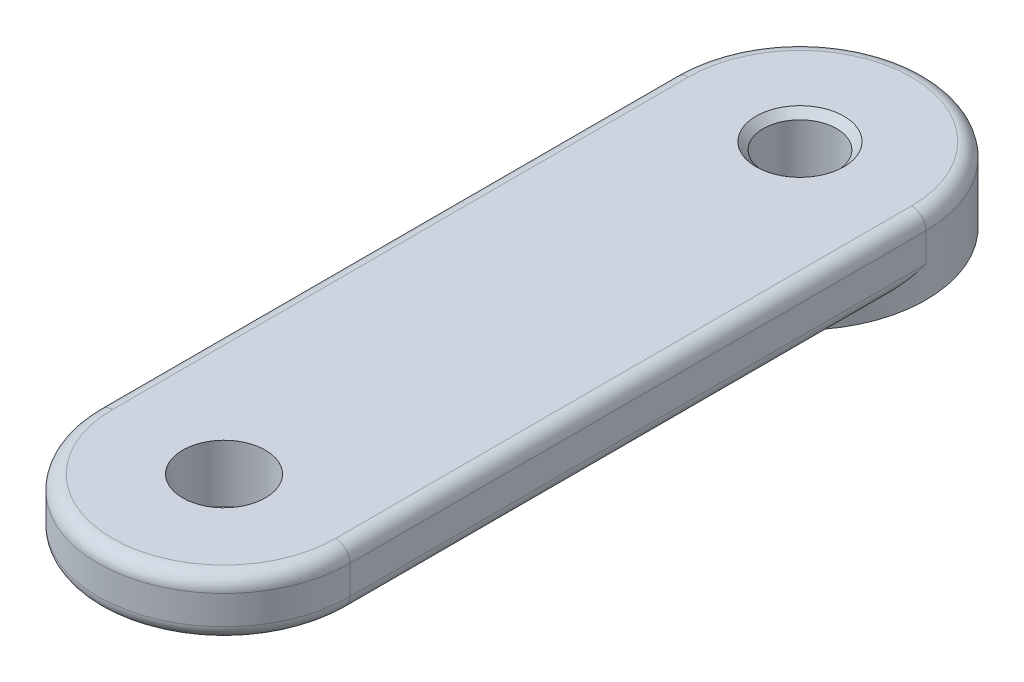
SolidWorks part; units mm, degrees
ref_plane "Front Plane" through (0, 0, 0) normal (0, 0, 1) x (1, 0, 0)
ref_plane "Top Plane" through (0, 0, 0) normal (0, 1, 0) x (1, 0, 0)
ref_plane "Right Plane" through (0, 0, 0) normal (1, 0, 0) x (0, 0, -1)
sketch "Sketch1" plane through (0, 0, 0) normal (0, 1, 0) x (1, 0, 0)
  line L0 (-8.75, 0) -> (-8.75, 40)
  line L1 (-8.75, 40) -> (0, 40) construction
  line L2 (8.75, 40) -> (8.75, 0)
  arc A0 (-8.75, 0) -> (8.75, 0) centre (0, 0) ccw
  arc A1 (8.75, 40) -> (-8.75, 40) centre (0, 40) ccw
  circle A2 centre (0, 40) radius 2.55
  circle A3 centre (0, 0) radius 2.875
  dimension "D1" = 17.5
  dimension "D2" = 5.75
  dimension "D3" = 5.1
  dimension "D4" = 40
extrude "Boss-Extrude1" add sketch "Sketch1" along normal blind 4
sketch "Sketch2" plane through (0, 4, 0) normal (0, 1, 0) x (1, 0, 0)
  arc A0 (-0.5856, -4.3609) -> (-0.1996, -3.4933) centre (-1.7886, -3.306) ccw
  arc A1 (-0.1996, -3.4933) -> (0.1996, -3.4933) centre (0, 0) ccw
  arc A2 (0.1996, -3.4933) -> (0.5856, -4.3609) centre (1.7886, -3.306) ccw
  arc A3 (0.5856, -4.3609) -> (0.7906, -4.3284) centre (0, 0) ccw
  arc A4 (0.7906, -4.3284) -> (0.8897, -3.384) centre (-0.6795, -3.6969) ccw
  arc A5 (0.8897, -3.384) -> (1.2693, -3.2607) centre (0, 0) ccw
  arc A6 (1.2693, -3.2607) -> (1.9045, -3.9665) centre (2.7226, -2.5914) ccw
  arc A7 (1.9045, -3.9665) -> (2.0895, -3.8722) centre (0, 0) ccw
  arc A8 (2.0895, -3.8722) -> (1.8918, -2.9435) centre (0.4962, -3.7259) ccw
  arc A9 (1.8918, -2.9435) -> (2.2148, -2.7088) centre (0, 0) ccw
  arc A10 (2.2148, -2.7088) -> (3.037, -3.1838) centre (3.3902, -1.6233) ccw
  arc A11 (3.037, -3.1838) -> (3.1838, -3.037) centre (0, 0) ccw
  arc A12 (3.1838, -3.037) -> (2.7088, -2.2148) centre (1.6233, -3.3902) ccw
  arc A13 (2.7088, -2.2148) -> (2.9435, -1.8918) centre (0, 0) ccw
  arc A14 (2.9435, -1.8918) -> (3.8722, -2.0895) centre (3.7259, -0.4962) ccw
  arc A15 (3.8722, -2.0895) -> (3.9665, -1.9045) centre (0, 0) ccw
  arc A16 (3.9665, -1.9045) -> (3.2607, -1.2693) centre (2.5914, -2.7226) ccw
  arc A17 (3.2607, -1.2693) -> (3.384, -0.8897) centre (0, 0) ccw
  arc A18 (3.384, -0.8897) -> (4.3284, -0.7906) centre (3.6969, 0.6795) ccw
  arc A19 (4.3284, -0.7906) -> (4.3609, -0.5856) centre (0, 0) ccw
  arc A20 (4.3609, -0.5856) -> (3.4933, -0.1996) centre (3.306, -1.7886) ccw
  arc A21 (3.4933, -0.1996) -> (3.4933, 0.1996) centre (0, 0) ccw
  arc A22 (3.4933, 0.1996) -> (4.3609, 0.5856) centre (3.306, 1.7886) ccw
  arc A23 (4.3609, 0.5856) -> (4.3284, 0.7906) centre (0, 0) ccw
  arc A24 (4.3284, 0.7906) -> (3.384, 0.8897) centre (3.6969, -0.6795) ccw
  arc A25 (3.384, 0.8897) -> (3.2607, 1.2693) centre (0, 0) ccw
  arc A26 (3.2607, 1.2693) -> (3.9665, 1.9045) centre (2.5914, 2.7226) ccw
  arc A27 (3.9665, 1.9045) -> (3.8722, 2.0895) centre (0, 0) ccw
  arc A28 (3.8722, 2.0895) -> (2.9435, 1.8918) centre (3.7259, 0.4962) ccw
  arc A29 (2.9435, 1.8918) -> (2.7088, 2.2148) centre (0, 0) ccw
  arc A30 (2.7088, 2.2148) -> (3.1838, 3.037) centre (1.6233, 3.3902) ccw
  arc A31 (3.1838, 3.037) -> (3.037, 3.1838) centre (0, 0) ccw
  arc A32 (3.037, 3.1838) -> (2.2148, 2.7088) centre (3.3902, 1.6233) ccw
  arc A33 (2.2148, 2.7088) -> (1.8918, 2.9435) centre (0, 0) ccw
  arc A34 (1.8918, 2.9435) -> (2.0895, 3.8722) centre (0.4962, 3.7259) ccw
  arc A35 (2.0895, 3.8722) -> (1.9045, 3.9665) centre (0, 0) ccw
  arc A36 (1.9045, 3.9665) -> (1.2693, 3.2607) centre (2.7226, 2.5914) ccw
  arc A37 (1.2693, 3.2607) -> (0.8897, 3.384) centre (0, 0) ccw
  arc A38 (0.8897, 3.384) -> (0.7906, 4.3284) centre (-0.6795, 3.6969) ccw
  arc A39 (0.7906, 4.3284) -> (0.5856, 4.3609) centre (0, 0) ccw
  arc A40 (0.5856, 4.3609) -> (0.1996, 3.4933) centre (1.7886, 3.306) ccw
  arc A41 (0.1996, 3.4933) -> (-0.1996, 3.4933) centre (0, 0) ccw
  arc A42 (-0.1996, 3.4933) -> (-0.5856, 4.3609) centre (-1.7886, 3.306) ccw
  arc A43 (-0.5856, 4.3609) -> (-0.7906, 4.3284) centre (0, 0) ccw
  arc A44 (-0.7906, 4.3284) -> (-0.8897, 3.384) centre (0.6795, 3.6969) ccw
  arc A45 (-0.8897, 3.384) -> (-1.2693, 3.2607) centre (0, 0) ccw
  arc A46 (-1.2693, 3.2607) -> (-1.9045, 3.9665) centre (-2.7226, 2.5914) ccw
  arc A47 (-1.9045, 3.9665) -> (-2.0895, 3.8722) centre (0, 0) ccw
  arc A48 (-2.0895, 3.8722) -> (-1.8918, 2.9435) centre (-0.4962, 3.7259) ccw
  arc A49 (-1.8918, 2.9435) -> (-2.2148, 2.7088) centre (0, 0) ccw
  arc A50 (-2.2148, 2.7088) -> (-3.037, 3.1838) centre (-3.3902, 1.6233) ccw
  arc A51 (-3.037, 3.1838) -> (-3.1838, 3.037) centre (0, 0) ccw
  arc A52 (-3.1838, 3.037) -> (-2.7088, 2.2148) centre (-1.6233, 3.3902) ccw
  arc A53 (-2.7088, 2.2148) -> (-2.9435, 1.8918) centre (0, 0) ccw
  arc A54 (-2.9435, 1.8918) -> (-3.8722, 2.0895) centre (-3.7259, 0.4962) ccw
  arc A55 (-3.8722, 2.0895) -> (-3.9665, 1.9045) centre (0, 0) ccw
  arc A56 (-3.9665, 1.9045) -> (-3.2607, 1.2693) centre (-2.5914, 2.7226) ccw
  arc A57 (-3.2607, 1.2693) -> (-3.384, 0.8897) centre (0, 0) ccw
  arc A58 (-3.384, 0.8897) -> (-4.3284, 0.7906) centre (-3.6969, -0.6795) ccw
  arc A59 (-4.3284, 0.7906) -> (-4.3609, 0.5856) centre (0, 0) ccw
  arc A60 (-4.3609, 0.5856) -> (-3.4933, 0.1996) centre (-3.306, 1.7886) ccw
  arc A61 (-3.4933, 0.1996) -> (-3.4933, -0.1996) centre (0, 0) ccw
  arc A62 (-3.4933, -0.1996) -> (-4.3609, -0.5856) centre (-3.306, -1.7886) ccw
  arc A63 (-4.3609, -0.5856) -> (-4.3284, -0.7906) centre (0, 0) ccw
  arc A64 (-4.3284, -0.7906) -> (-3.384, -0.8897) centre (-3.6969, 0.6795) ccw
  arc A65 (-3.384, -0.8897) -> (-3.2607, -1.2693) centre (0, 0) ccw
  arc A66 (-3.2607, -1.2693) -> (-3.9665, -1.9045) centre (-2.5914, -2.7226) ccw
  arc A67 (-3.9665, -1.9045) -> (-3.8722, -2.0895) centre (0, 0) ccw
  arc A68 (-3.8722, -2.0895) -> (-2.9435, -1.8918) centre (-3.7259, -0.4962) ccw
  arc A69 (-2.9435, -1.8918) -> (-2.7088, -2.2148) centre (0, 0) ccw
  arc A70 (-2.7088, -2.2148) -> (-3.1838, -3.037) centre (-1.6233, -3.3902) ccw
  arc A71 (-3.1838, -3.037) -> (-3.037, -3.1838) centre (0, 0) ccw
  arc A72 (-3.037, -3.1838) -> (-2.2148, -2.7088) centre (-3.3902, -1.6233) ccw
  arc A73 (-2.2148, -2.7088) -> (-1.8918, -2.9435) centre (0, 0) ccw
  arc A74 (-1.8918, -2.9435) -> (-2.0895, -3.8722) centre (-0.4962, -3.7259) ccw
  arc A75 (-2.0895, -3.8722) -> (-1.9045, -3.9665) centre (0, 0) ccw
  arc A76 (-1.9045, -3.9665) -> (-1.2693, -3.2607) centre (-2.7226, -2.5914) ccw
  arc A77 (-1.2693, -3.2607) -> (-0.8897, -3.384) centre (0, 0) ccw
  arc A78 (-0.8897, -3.384) -> (-0.7906, -4.3284) centre (0.6795, -3.6969) ccw
  arc A79 (-0.7906, -4.3284) -> (-0.5856, -4.3609) centre (0, 0) ccw
extrude "Cut-Extrude1" [suppressed] cut sketch "Sketch2" against normal blind 10
sketch "Sketch3" plane through (0, 0, 0) normal (0, -1, 0) x (1, 0, 0)
  circle A0 centre (0, -40) radius 8.75
  arc A1 (-8.75, -40) -> (8.75, -40) centre (0, -40) ccw construction
  circle A2 centre (0, -40) radius 2.55 construction
  circle A3 centre (0, -40) radius 2.55
extrude "Boss-Extrude2" add sketch "Sketch3" along normal blind 5
fillet "Fillet1" [suppressed] radius 2.5
fillet "Fillet2" radius 1 8 edges at (-8.75, 0, -20) (0, 0, 8.75) (0, 4, 8.75) (-8.75, 4, -20) (0, 4, -48.75) (0, -5, -48.75) (8.75, 0, -20) (8.75, 4, -20)
chamfer "Chamfer1" distance 0.5 angle 45 2 edges at (0, -5, -42.55) (0, 4, -37.45)
sketch "Sketch4" plane through (0, 4, 0) normal (0, 1, 0) x (1, 0, 0)
  circle A0 centre (0, 0) radius 5.375
  circle A1 centre (0, 0) radius 2.875 construction
  circle A2 centre (0, 0) radius 2.875
  dimension "D1" = 2.5
extrude "Boss-Extrude3" [suppressed] add sketch "Sketch4" along normal blind 3
fillet "Fillet3" [suppressed] radius 3
chamfer "Chamfer2" [suppressed] distance 0.5 angle 45
fillet "Fillet4" [suppressed] radius 1
sketch "Sketch5" plane through (0, -5, 0) normal (0, -1, 0) x (1, 0, 0)
  circle A0 centre (0, -40) radius 8.75 construction
  circle A1 centre (0, -40) radius 8.75
extrude "Cut-Extrude2" cut sketch "Sketch5" against normal blind 3.84
